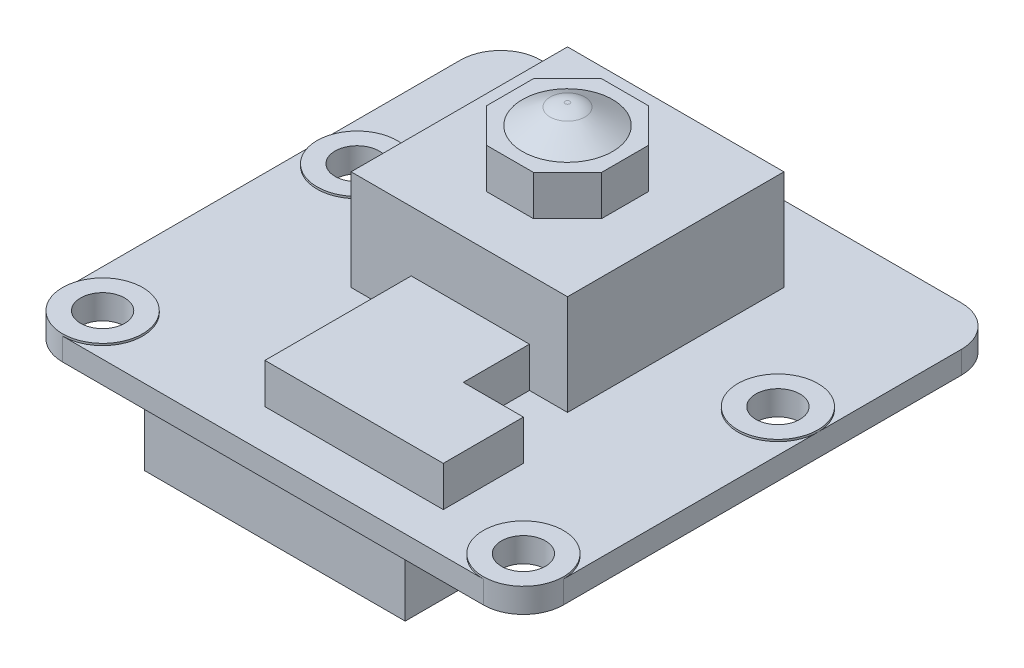
SolidWorks part; units mm, degrees
ref_plane "Front Plane" through (0, 0, 0) normal (0, 0, 1) x (1, 0, 0)
ref_plane "Top Plane" through (0, 0, 0) normal (0, 1, 0) x (1, 0, 0)
ref_plane "Right Plane" through (0, 0, 0) normal (1, 0, 0) x (0, 0, -1)
sketch "Sketch1" plane through (0, 0, 0) normal (0, 1, 0) x (1, 0, 0)
  line L0 (-2.875, 5.644) -> (2.875, 5.644)
  line L1 (-12.5, -11.931) -> (12.5, -11.931)
  line L2 (-12.5, -11.931) -> (-12.5, 11.931)
  line L3 (-12.5, 11.931) -> (12.5, 11.931)
  line L4 (12.5, -11.931) -> (12.5, 11.931)
  line L5 (-12.5, -11.931) -> (12.5, 11.931) construction
  line L6 (-12.5, 11.931) -> (12.5, -11.931) construction
  line L7 (-5.4, -2.631) -> (5.4, -2.631)
  line L8 (-5.4, -2.631) -> (-5.4, 8.169)
  line L9 (-5.4, 8.169) -> (5.4, 8.169)
  line L10 (5.4, -2.631) -> (5.4, 8.169)
  line L11 (-5.4, -2.631) -> (5.4, 8.169) construction
  line L12 (-5.4, 8.169) -> (5.4, -2.631) construction
  line L13 (2.875, -0.106) -> (2.875, 5.644)
  line L14 (-2.875, -0.106) -> (2.875, -0.106)
  line L15 (-2.875, -0.106) -> (-2.875, 5.644)
  line L16 (3.5, -2.631) -> (3.5, -5.931)
  line L17 (3.5, -5.931) -> (6.5, -5.931)
  line L18 (6.5, -5.931) -> (6.5, -9.931)
  line L19 (-2.4, -2.631) -> (-2.4, -9.931)
  line L20 (-2.4, -9.931) -> (6.5, -9.931)
  circle A0 centre (-10.5, -9.931) radius 2
  circle A1 centre (-10.5, -9.931) radius 1.1
  circle A2 centre (10.5, -9.931) radius 1.1
  circle A3 centre (10.5, -9.931) radius 2
  circle A4 centre (10.5, 2.769) radius 1.1
  circle A5 centre (10.5, 2.769) radius 2
  circle A6 centre (-10.5, 2.769) radius 1.1
  circle A7 centre (-10.5, 2.769) radius 2
  circle A8 centre (-10.5, 9.931) radius 2
  circle A9 centre (10.5, 9.931) radius 2
  point P0 (0, 0)
  point P20 (0, 11.931)
  point P29 (0, 2.769)
  dimension "D3" = 4
  dimension "D7" = 10.8
  dimension "D1" = 25
  dimension "D2" = 23.862
  dimension "D8" = 7.3
  dimension "D9" = 5.75
  dimension "D10" = 3.3
  dimension "D11" = 8.9
  dimension "D12" = 3
  dimension "D13" = 3
  dimension "D4" = 0.9
  dimension "D5" = 2
  dimension "D6" = 2
extrude "Boss-Extrude1" add sketch "Sketch1" against normal blind 1.12 contours L2 A7 A0 L1 L19 L7 L8 L9 L10 L16 L17 L18 A3 L4 A5 L3 | A7 A6 | A0 A1 | A5 A4 | A3 A2 | L7 L19 L1 L18 L17 L16 | L7 L10 L9 L8 L14 L15 L0 L13 | L15 L14 L13 L0 | A8 | A9 region at (0, 0, -2.769) region at (8.5566, 0, -2.769) region at (-10.5, 0, -4.7124) region at (-8.8414, 0, 11.5896) region at (-11.8742, 0, 11.3052) region at (9.1258, 0, 8.5568) region at (-10.5, 0, -9.931) region at (10.5, 0, -9.931) region at (-5.2473, 0, -2.769) region at (1.5197, 0, 6.6405)
extrude "Boss-Extrude2" add sketch "Sketch1<3>" along normal blind 7 contours L15 L14 L13 L0 region at (0, 0, -2.769)
sketch "Sketch1<3>" plane through (0, 0, 0) normal (0, 1, 0) x (1, 0, 0) same geometry as "Sketch1"
extrude "Boss-Extrude3" add sketch "Sketch1<4>" along normal blind 5 contours L7 L10 L9 L8 L14 L15 L0 L13 region at (-5.2473, 0, -2.769)
sketch "Sketch1<4>" plane through (0, 0, 0) normal (0, 1, 0) x (1, 0, 0) same geometry as "Sketch1"
extrude "Boss-Extrude4" add sketch "Sketch1<6>" along normal blind 2 contours L19 L20 L18 L17 L16 L7 region at (1.5197, 0, 6.6405)
sketch "Sketch1<6>" plane through (0, 0, 0) normal (0, 1, 0) x (1, 0, 0) same geometry as "Sketch1"
extrude "Boss-Extrude5" add sketch "Sketch1<7>" along normal blind 0.1 contours A7 A6 | A0 A1 | A5 A4 | A3 A2 region at (8.5566, 0, -2.769) region at (-10.5, 0, -4.7124) region at (-11.8742, 0, 11.3052) region at (9.1258, 0, 8.5568)
sketch "Sketch1<7>" plane through (0, 0, 0) normal (0, 1, 0) x (1, 0, 0) same geometry as "Sketch1"
chamfer "Chamfer1" distance 1.7 angle 45 4 edges at (-2.875, 6, -5.644) (2.875, 6, -5.644) (2.875, 6, 0.106) (-2.875, 6, 0.106)
sketch "Sketch3" plane through (0, 7, 0) normal (0, 1, 0) x (1, 0, 0)
  line L0 (2.875, 1.594) -> (2.875, 3.944) construction
  line L1 (-1.175, 5.644) -> (1.175, 5.644) construction
  circle A0 centre (0, 2.769) radius 2.25
  point P2 (0, 0)
  point P5 (2.875, 2.769)
  point P8 (0, 5.644)
  dimension "D1" = 4.5
extrude "Boss-Extrude6" add sketch "Sketch3" along normal blind 1 draft 60
fillet "Fillet1" radius 1.5 1 edges at (0, 8, -2.2511)
sketch "Sketch4" plane through (0, -1.12, 0) normal (0, -1, 0) x (1, 0, 0)
  line L1 (-6.5, 7.831) -> (6.5, 7.831)
  line L2 (-6.5, 7.831) -> (-6.5, 11.831)
  line L3 (-6.5, 11.831) -> (6.5, 11.831)
  line L4 (6.5, 7.831) -> (6.5, 11.831)
  line L5 (-6.5, 7.831) -> (6.5, 11.831) construction
  line L6 (-6.5, 11.831) -> (6.5, 7.831) construction
  line L7 (-10.5, -11.931) -> (10.5, -11.931) construction
  line L8 (-10.5, 11.931) -> (10.5, 11.931) construction
  point P0 (0, 9.831)
  point P7 (0, 0)
  point P10 (0, -11.931)
  dimension "D1" = 13
  dimension "D2" = 4
  dimension "D3" = 0.1
extrude "Boss-Extrude7" add sketch "Sketch4" along normal blind 2.75
